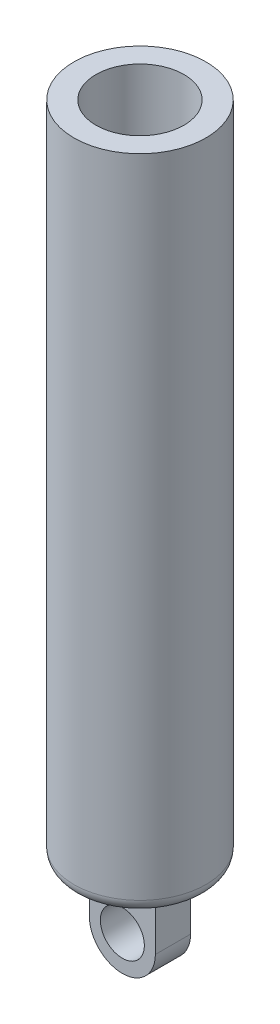
SolidWorks part; units mm, degrees
ref_plane "Front Plane" through (0, 0, 0) normal (0, 0, 1) x (1, 0, 0)
ref_plane "Top Plane" through (0, 0, 0) normal (0, 1, 0) x (1, 0, 0)
ref_plane "Right Plane" through (0, 0, 0) normal (1, 0, 0) x (0, 0, -1)
sketch "Sketch1" plane through (0, 0, 0) normal (0, 1, 0) x (1, 0, 0)
  circle A0 centre (0, 0) radius 15
  point P3 (0, 0)
  dimension "D1" = 30
extrude "Boss-Extrude1" add sketch "Sketch1" along normal blind 150
shell "Shell1" thickness 5 removed face at (0, 150, 15)
fillet "Fillet1" radius 3 1 edges at (0, 0, 15)
sketch "Sketch2" plane through (0, 0, 0) normal (0, -1, 0) x (1, 0, 0)
  line L1 (-7.5, -4) -> (7.5, -4)
  line L2 (-7.5, -4) -> (-7.5, 4)
  line L3 (-7.5, 4) -> (7.5, 4)
  line L4 (7.5, -4) -> (7.5, 4)
  line L5 (-7.5, -4) -> (7.5, 4) construction
  line L6 (-7.5, 4) -> (7.5, -4) construction
  point P0 (0, 0)
  dimension "D1" = 8
  dimension "D2" = 15
extrude "Boss-Extrude2" add sketch "Sketch2" along normal blind 20 separate body
sketch "Sketch3" plane through (0, 0, 4) normal (0, 0, 1) x (1, 0, 0)
  line L0 (7.5, -20) -> (-7.5, -20) construction
  line L1 (7.5, -20) -> (7.5, 0) construction
  circle A0 centre (0, -12) radius 5
  point P2 (0, 0)
  point P5 (0, 0)
  dimension "D1" = 10
  dimension "D2" = 8
  dimension "D3" = 7.5
extrude "Cut-Extrude1" cut sketch "Sketch3" against normal through all
fillet "Fillet3" radius 7.5 2 edges at (7.5, -20, 0) (-7.5, -20, 0)
equation "\"20i\"=35"
